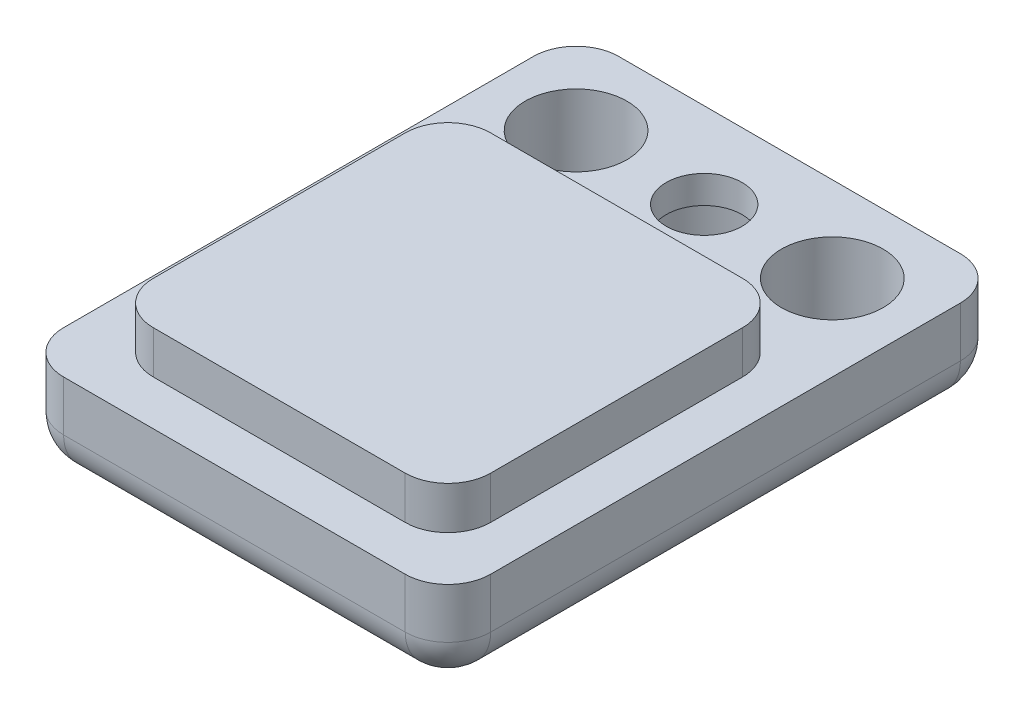
SolidWorks part; units mm, degrees
ref_plane "Front Plane" through (0, 0, 0) normal (0, 0, 1) x (1, 0, 0)
ref_plane "Top Plane" through (0, 0, 0) normal (0, 1, 0) x (1, 0, 0)
ref_plane "Right Plane" through (0, 0, 0) normal (1, 0, 0) x (0, 0, -1)
sketch "Sketch1" plane through (0, 0, 0) normal (0, 1, 0) x (1, 0, 0)
  line L1 (5, -6.5) -> (-5, -6.5)
  line L2 (5, -6.5) -> (5, 6.5)
  line L3 (5, 6.5) -> (-5, 6.5)
  line L4 (-5, -6.5) -> (-5, 6.5)
  line L5 (5, -6.5) -> (-5, 6.5) construction
  line L6 (5, 6.5) -> (-5, -6.5) construction
  point P0 (0, 0)
  dimension "D1" = 10
  dimension "D2" = 13
extrude "Extrude1" add sketch "Sketch1" along normal blind 2.175
sketch "Sketch3" plane through (0, 2.175, 0) normal (0, 1, 0) x (1, 0, 0)
  line L0 (-5, 6.5) -> (-5, -6.5) construction
  line L1 (-3.95, -5.45) -> (3.95, -5.45)
  line L2 (-3.95, -5.45) -> (-3.95, 2.45)
  line L3 (-3.95, 2.45) -> (3.95, 2.45)
  line L4 (3.95, -5.45) -> (3.95, 2.45)
  line L5 (-5, -6.5) -> (5, -6.5) construction
  dimension "D1" = 7.9
  dimension "D2" = 7.9
  dimension "D3" = 1.05
  dimension "D4" = 1.05
extrude "Extrude3" add sketch "Sketch3" along normal blind 1
hole_wizard "CBORE for #0 Socket Head Cap Screw1" positions "3DSketch3" profile "Sketch8" counterbore size "#0" standard "Ansi Inch" end condition through all
sketch3d "3DSketch3"
  line L0 (5, 0, -6.5) -> (-5, 0, -6.5) construction
  line L1 (-5, 0, -6.5) -> (-5, 0, 6.5) construction
  point P0 (0, 0, -4.5)
  dimension "D1" = 2
  dimension "D2" = 5
sketch "Sketch8" plane through (0, 0, -4.5) normal (1, 0, 0) x (0, 0, -1)
  line L0 (0, 0) -> (0, 3.175)
  line L1 (0, 3.175) -> (0.889, 3.175)
  line L3 (0.889, 3.175) -> (0.889, 1.524)
  line L4 (0.889, 1.524) -> (1.5875, 1.524)
  line L5 (1.5875, 1.524) -> (1.5875, 0)
  line L7 (1.5875, 0) -> (0, 0)
  line L11 (0, -6.35) -> (0, 107.95) construction
  dimension "Thru Hole Dia." = 1.778
  dimension "Thru Hole Depth" = 3.175
  dimension "C'Bore Dia." = 3.175
  dimension "C'Bore Depth" = 1.524
hole_wizard "3/32 (0.09375) Diameter Hole1" positions "3DSketch4" profile "Sketch9" hole size "3/32" standard "Ansi Inch"
sketch3d "3DSketch4"
  line L0 (5, 0, -6.5) -> (-5, 0, -6.5) construction
  line L1 (-5, 0, -6.5) -> (-5, 0, 6.5) construction
  line L2 (5, 0, 6.5) -> (5, 0, -6.5) construction
  point P0 (-3, 0, -4.5)
  point P2 (3, 0, -4.5)
  dimension "D1" = 2
  dimension "D2" = 2
  dimension "D3" = 2
  dimension "D4" = 2
sketch "Sketch9" plane through (-3, 0, -4.5) normal (1, 0, 0) x (0, 0, -1)
  line L0 (0, 0) -> (0, 10.7154)
  line L1 (0, 10.7154) -> (1.1906, 10)
  line L2 (1.1906, 10) -> (1.1906, 0)
  line L5 (1.1906, 0) -> (0, 0)
  line L10 (0, 10.7154) -> (-1.1906, 10) construction
  line L11 (0, -6.35) -> (0, 107.95) construction
  dimension "Hole Dia." = 2.3812
  dimension "Hole Depth" = 10
  dimension "Drill Angle" = 118
fillet "Fillet3" radius 1 12 edges at (0, 0, -6.5) (5, 0, 0) (-5, 0, 0) (0, 0, 6.5) (5, 1.0875, 6.5) (3.95, 2.675, 5.45) (3.95, 2.675, -2.45) (5, 1.0875, -6.5) (-5, 1.0875, -6.5) (-3.95, 2.675, -2.45) (-5, 1.0875, 6.5) (-3.95, 2.675, 5.45)
